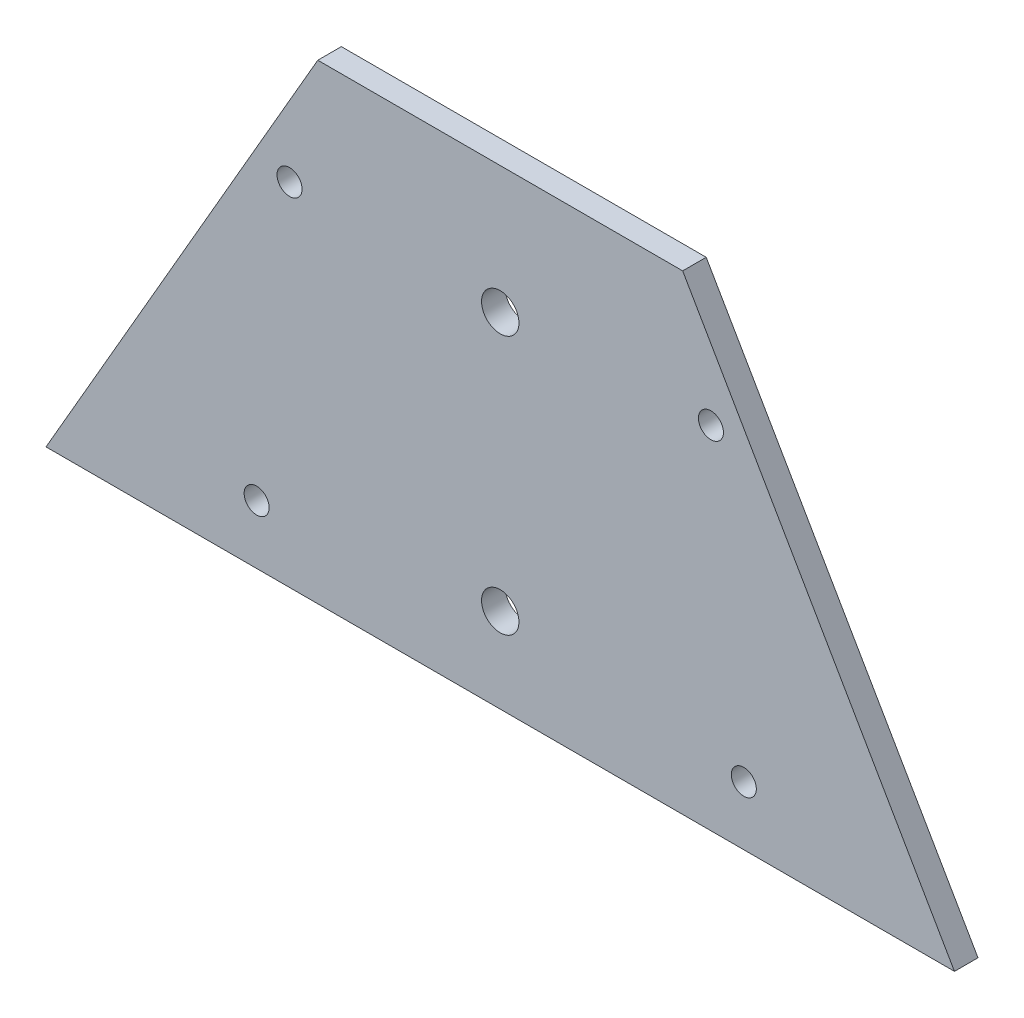
SolidWorks part; units mm, degrees
material "6061-T6 (SS)"
ref_plane "Front" through (0, 0, 0) normal (0, 0, 1) x (1, 0, 0)
ref_plane "Top" through (0, 0, 0) normal (0, 1, 0) x (1, 0, 0)
ref_plane "Right" through (0, 0, 0) normal (1, 0, 0) x (0, 0, -1)
sketch "Sketch1" plane through (0, 0, 0) normal (0, 0, 1) x (1, 0, 0)
  line L0 (-49.2125, 113.0795) -> (49.2125, 113.0795)
  line L1 (-122.536, -13.9205) -> (0, 0) construction
  line L2 (-49.2125, 113.0795) -> (0, 0) construction
  line L3 (49.2125, 113.0795) -> (122.536, -13.9205)
  line L4 (122.536, -13.9205) -> (-122.536, -13.9205)
  line L5 (122.536, -13.9205) -> (73.3235, -99.159) construction
  line L6 (73.3235, -99.159) -> (-73.3235, -99.159) construction
  line L7 (-73.3235, -99.159) -> (-122.536, -13.9205) construction
  line L8 (-122.536, -13.9205) -> (-49.2125, 113.0795)
  line L9 (0, 0) -> (49.2125, 113.0795) construction
  line L10 (0, 0) -> (122.536, -13.9205) construction
  line L11 (0, 0) -> (73.3235, -99.159) construction
  line L13 (0, 0) -> (-73.3235, -99.159) construction
  dimension "D1" = 98.425
  dimension "D2" = 127
extrude "Boss-Extrude1" add sketch "Sketch1" along normal blind 6.35
ref_axis "Axis1" through (0, 0, 0) along (0, 0, 1)
sketch "Sketch2" plane through (0, 0, 6.35) normal (0, 0, 1) x (1, 0, 0)
  line L0 (0, 0) -> (0, 78.8054) construction
  line L1 (0, 0) -> (0, 8.9554) construction
  line L3 (49.2125, 113.0795) -> (-49.2125, 113.0795) construction
  line L4 (56.8386, 80.8207) -> (93.2066, 17.8295) construction
  line L5 (93.2066, 17.8295) -> (65.7103, 1.9545) construction
  line L6 (65.7103, 1.9545) -> (29.3423, 64.9457) construction
  line L7 (29.3423, 64.9457) -> (56.8386, 80.8207) construction
  line L9 (122.536, -13.9205) -> (49.2125, 113.0795) construction
  line L10 (-122.536, -13.9205) -> (122.536, -13.9205) construction
  point P12 (122.536, -13.9205)
  dimension "D1" = 69.85
  dimension "D2" = 34.2741
  dimension "D3" = 9.525
  dimension "D4" = 31.75
  dimension "D5" = 31.75
  dimension "D6" = 15.875
hole_wizard "3/8 Clearance Hole1" positions "Sketch4" profile "Sketch3" hole size "3/8" standard "ANSI Inch" end condition through all
sketch "Sketch4" plane through (0, 0, 6.35) normal (0, 0, 1) x (1, 0, 0)
  point P0 (0, 78.8054)
  point P3 (0, 8.9554)
sketch "Sketch3" plane through (0, 78.8054, 6.35) normal (1, 0, 0) x (0, -1, 0)
  line L0 (0, 0) -> (0, 6.35)
  line L1 (0, 6.35) -> (5.0419, 6.35)
  line L2 (5.0419, 6.35) -> (5.0419, 0)
  line L5 (5.0419, 0) -> (0, 0)
  line L11 (0, -6.35) -> (0, 107.95) construction
  dimension "Thru Hole Dia." = 10.0838
  dimension "Thru Hole Depth" = 6.35
hole_wizard "1/4 Clearance Hole1" positions "Sketch6" profile "Sketch5" hole size "1/4" standard "ANSI Inch" end condition through all
sketch "Sketch6" plane through (0, 0, 6.35) normal (0, 0, 1) x (1, 0, 0)
  point P9 (65.7103, 1.9545)
  point P16 (56.8386, 80.8207)
sketch "Sketch5" plane through (65.7103, 1.9545, 6.35) normal (1, 0, 0) x (0, -1, 0)
  line L0 (0, 0) -> (0, 6.35)
  line L1 (0, 6.35) -> (3.3782, 6.35)
  line L2 (3.3782, 6.35) -> (3.3782, 0)
  line L5 (3.3782, 0) -> (0, 0)
  line L11 (0, -6.35) -> (0, 107.95) construction
  dimension "Thru Hole Dia." = 6.7564
  dimension "Thru Hole Depth" = 6.35
mirror "Mirror1" about plane through (0, 0, 0) normal (1, 0, 0) of "1/4 Clearance Hole1"
